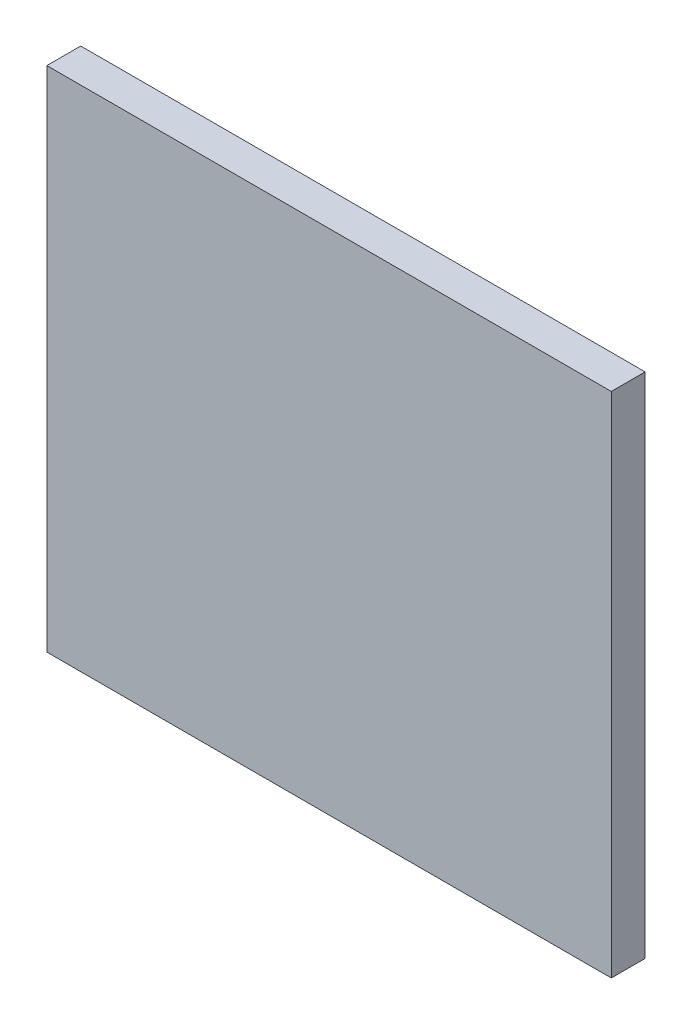
SolidWorks part; units mm, degrees
ref_plane "Front Plane" through (0, 0, 0) normal (0, 0, 1) x (1, 0, 0)
ref_plane "Top Plane" through (0, 0, 0) normal (0, 1, 0) x (1, 0, 0)
ref_plane "Right Plane" through (0, 0, 0) normal (1, 0, 0) x (0, 0, -1)
sketch "Sketch1" plane through (0, 0, 0) normal (0, 0, 1) x (1, 0, 0)
  line L1 (-50, 45) -> (0, 45)
  line L2 (-50, 45) -> (-50, 0)
  line L3 (-50, 0) -> (0, 0)
  line L4 (0, 45) -> (0, 0)
  dimension "D1" = 50
  dimension "D2" = 45
extrude "Boss-Extrude1" add sketch "Sketch1" along normal blind 3
